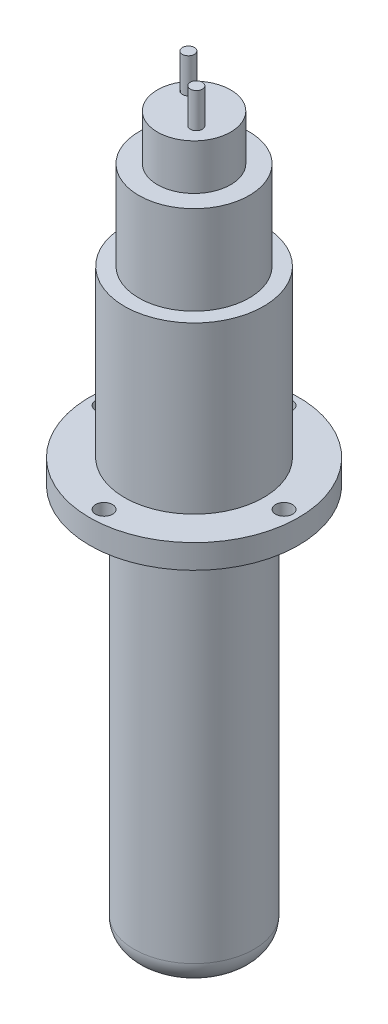
SolidWorks part; units mm, degrees
material "6061 Alloy"
ref_plane "Front" through (0, 0, 0) normal (0, 0, 1) x (1, 0, 0)
ref_plane "Top" through (0, 0, 0) normal (0, 1, 0) x (1, 0, 0)
ref_plane "Right" through (0, 0, 0) normal (1, 0, 0) x (0, 0, -1)
sketch "Sketch1" plane through (0, 0, 0) normal (0, 1, 0) x (1, 0, 0)
  circle A0 centre (0, 0) radius 22.098
  dimension "D1" = 44.196
extrude "Boss-Extrude1" add sketch "Sketch1" along normal blind 5.08
sketch "Sketch2" plane through (0, 5.08, 0) normal (0, 1, 0) x (1, 0, 0)
  circle A0 centre (0, 0) radius 14.732
  dimension "D1" = 29.464
extrude "Boss-Extrude2" add sketch "Sketch2" along normal blind 35.052
sketch "Sketch3" plane through (0, 40.132, 0) normal (0, 1, 0) x (1, 0, 0)
  circle A0 centre (0, 0) radius 11.684
  dimension "D1" = 23.368
extrude "Boss-Extrude3" add sketch "Sketch3" along normal blind 18.796
sketch "Sketch4" plane through (0, 58.928, 0) normal (0, 1, 0) x (1, 0, 0)
  circle A0 centre (0, 0) radius 7.747
  dimension "D1" = 15.494
extrude "Boss-Extrude4" add sketch "Sketch4" along normal blind 9.652
sketch "Sketch5" plane through (0, 68.58, 0) normal (0, 1, 0) x (1, 0, 0)
  circle A0 centre (-4.2434, 3.0444) radius 1.27
  circle A1 centre (2.97, -2.4818) radius 1.27
  dimension "D1" = 2.54
  dimension "D2" = 2.54
extrude "Boss-Extrude5" add sketch "Sketch5" along normal blind 7.366
sketch "Sketch6" plane through (0, 5.08, 0) normal (0, 1, 0) x (1, 0, 0)
  circle A0 centre (0, 19.05) radius 1.7907
  point P2 (0, 19.05)
  dimension "D1" = 3.5814
  dimension "D2" = 19.05
extrude "Cut-Extrude1" cut sketch "Sketch6" against normal blind 7.366
pattern_circular "CirPattern1" count 4 over 360 about axis through (0, 5.08, 0) along (0, 1, 0) of "Cut-Extrude1"
sketch "Sketch7" plane through (0, 0, 0) normal (0, -1, 0) x (-1, 0, 0)
  circle A0 centre (0, 0) radius 12.7
  dimension "D1" = 25.4
extrude "Boss-Extrude6" add sketch "Sketch7" along normal blind 83.82
fillet "Fillet1" radius 5.08 1 edges at (0, -83.82, -12.7)
